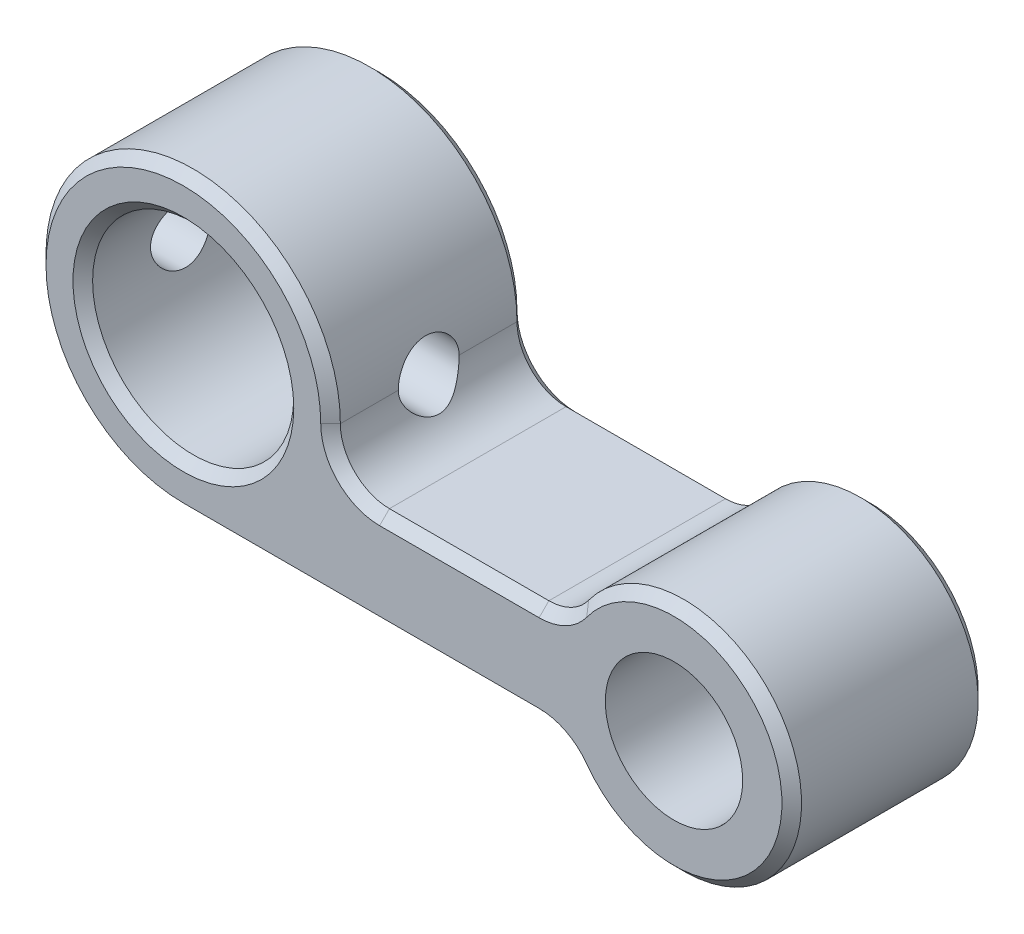
SolidWorks part; units mm, degrees
ref_plane "前视基准面" through (0, 0, 0) normal (0, 0, 1) x (1, 0, 0)
ref_plane "上视基准面" through (0, 0, 0) normal (0, 1, 0) x (1, 0, 0)
ref_plane "右视基准面" through (0, 0, 0) normal (1, 0, 0) x (0, 0, -1)
sketch "草图1" plane through (0, 0, 0) normal (0, 0, 1) x (1, 0, 0)
  circle A0 centre (0, 0) radius 10.25
  circle A1 centre (0, 0) radius 15
extrude "凸台-拉伸1" add sketch "草图1" along normal mid plane 20
sketch "草图2" plane through (0, 0, 0) normal (1, 0, 0) x (0, 0, -1)
  circle A0 centre (0, 0) radius 3.1
extrude "切除-拉伸1" cut sketch "草图2" against normal through all both and the other way through all
sketch "草图3" plane through (0, 0, 0) normal (0, 0, 1) x (1, 0, 0)
  line L0 (0, 0) -> (0, -15) construction
  line L1 (0, -15) -> (50, -15) construction
  line L2 (50, -15) -> (50, -10) construction
  line L3 (50, -10) -> (50, -5) construction
  line L4 (50, -10) -> (11.1803, -10) construction
  line L5 (50, -5) -> (14.1421, -5) construction
  line L6 (0, -15) -> (0, -20) construction
  line L7 (0, -20) -> (50, -20) construction
  line L8 (50, -20) -> (50, -15) construction
  circle A0 centre (0, 0) radius 15 construction
  circle A1 centre (50, -10) radius 5 construction
  circle A6 centre (50, -10) radius 12
  circle A7 centre (50, -10) radius 7
extrude "凸台-拉伸2" add sketch "草图3" along normal mid plane 20 separate body
sketch "草图4" plane through (0, 0, 0) normal (0, 0, 1) x (1, 0, 0)
  line L0 (0, 0) -> (0, -10) construction
  line L2 (40.202, -15) -> (0, -15)
  line L4 (40.202, -5) -> (14.1421, -5)
  arc A0 (0, -15) -> (14.1421, -5) centre (0, 0) ccw
  circle A2 centre (0, 0) radius 15 construction
  arc A3 (40.202, -5) -> (40.202, -15) centre (50, -10) ccw
extrude "凸台-拉伸3" add sketch "草图4" along normal mid plane 20
fillet "圆角1" radius 5 3 edges at (14.1421, -5, 0) (39.0913, -15, 0) (39.0913, -5, 0)
chamfer "倒角1" distance 1 angle 45 16 edges at (38.521, -15.5443, -10) (18.1261, -15, -10) (62, -10, -10) (-10.6066, 10.6066, -10) (38.521, -4.4557, -10) (16.4645, -3.5355, -10) (28.1261, -5, -10) (10.25, 0, -10) (10.25, 0, 10) (38.521, -4.4557, 10) (62, -10, 10) (28.1261, -5, 10) (38.521, -15.5443, 10) (16.4645, -3.5355, 10) (18.1261, -15, 10) (-10.6066, 10.6066, 10)
